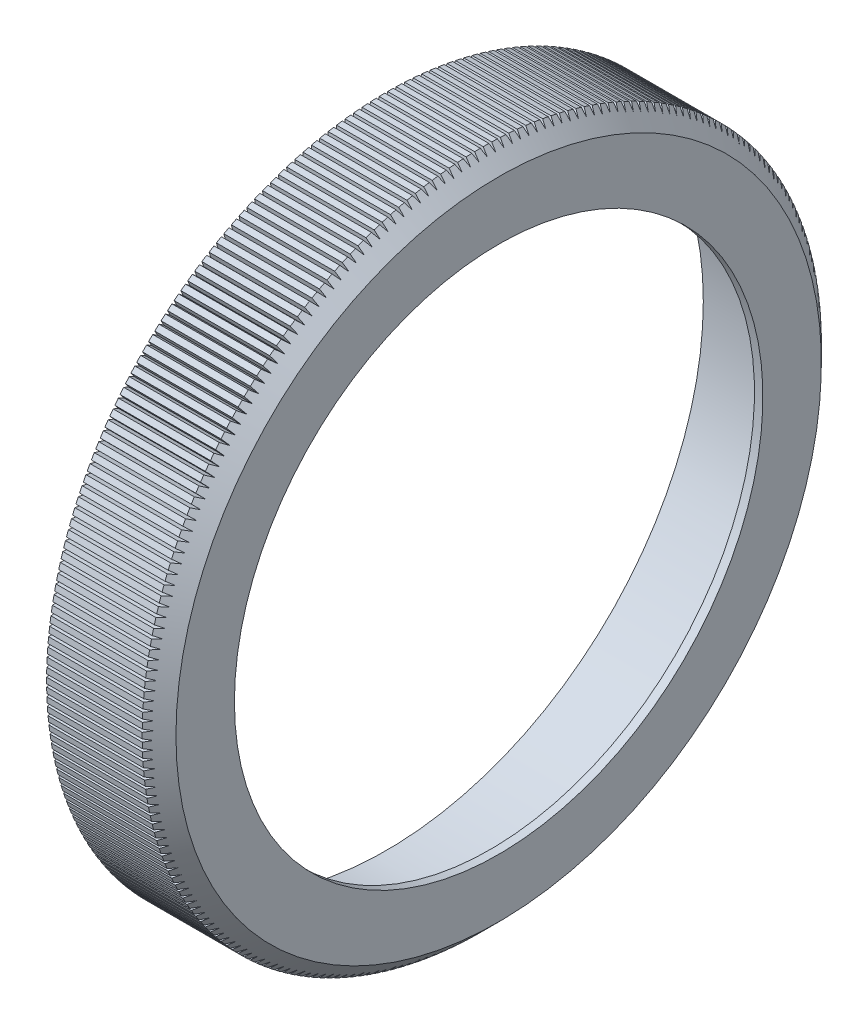
SolidWorks part; units mm, degrees
material "6061-T6 (SS)"
ref_plane "Plan de face" through (0, 0, 0) normal (0, 0, 1) x (1, 0, 0)
ref_plane "Plan de dessus" through (0, 0, 0) normal (0, 1, 0) x (1, 0, 0)
ref_plane "Plan de droite" through (0, 0, 0) normal (1, 0, 0) x (0, 0, -1)
sketch "Esquisse1" plane through (0, 0, 0) normal (0, 0, 1) x (1, 0, 0)
  line L0 (15.5, 56.4) -> (34, 56.4)
  line L1 (34, 56.4) -> (34, 47)
  line L2 (34, 47) -> (35.5, 47)
  line L3 (35.5, 47) -> (35.5, 60.4)
  line L4 (35.5, 60.4) -> (15.5, 60.4)
  line L5 (15.5, 60.4) -> (15.5, 56.4)
  line L6 (19, 56.4) -> (3, 56.4) construction
  line L7 (34, -57.9) -> (34, 57.9) construction
  line L8 (0, 0) -> (13.8595, 0) construction
  dimension "D1" = 4
  dimension "D2" = 1.5
  dimension "D3" = 47
  dimension "D4" = 20
revolve "Révolution1" add sketch "Esquisse1" angle 360 about L8
chamfer "Chanfrein1" distance 3 angle 45 1 edges at (35.5, 0, 60.4)
sketch "Esquisse2" plane through (35.5, 0, 0) normal (1, 0, 0) x (0, 0, -1)
  line L0 (0, 0) -> (0, 60.4) construction
  line L1 (-0.25, 60.4) -> (0, 59.4)
  line L2 (0, 59.4) -> (0.25, 60.4)
  line L3 (0.25, 60.4) -> (-0.25, 60.4)
  circle A0 centre (0, 0) radius 60.4 construction
  dimension "D1" = 0.5
  dimension "D2" = 1
extrude "Enlèv. mat.-Extru.1" cut sketch "Esquisse2" against normal through all
pattern_circular "Répétition circulaire1" count 250 over 360 about axis through (35.5, 0, 0) along (-1, 0, 0) of "Enlèv. mat.-Extru.1"
